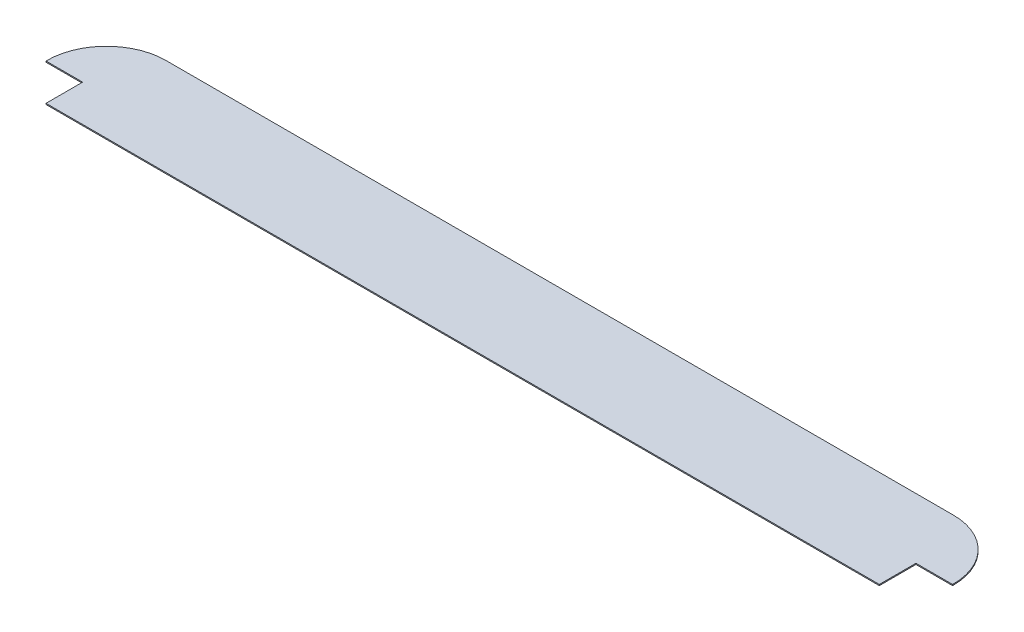
SolidWorks part; units mm, degrees
material "AISI 1020 Steel, Cold Rolled"
ref_plane "Front Plane" through (0, 0, 0) normal (0, 0, 1) x (1, 0, 0)
ref_plane "Top Plane" through (0, 0, 0) normal (0, 1, 0) x (1, 0, 0)
ref_plane "Right Plane" through (0, 0, 0) normal (1, 0, 0) x (0, 0, -1)
sketch "Sketch1" plane through (0, 0, 0) normal (0, 1, 0) x (1, 0, 0)
  line L1 (-455, -53) -> (455, -53)
  line L2 (-495, -13) -> (-495, -12)
  line L3 (-430, 53) -> (430, 53)
  line L4 (495, -13) -> (495, -12)
  line L5 (-455, -48.7172) -> (495, 53) construction
  line L6 (-495, 53) -> (455, -48.7172) construction
  line L9 (-495, -13) -> (-455, -13)
  line L10 (-455, -53) -> (-455, -13)
  line L13 (495, -13) -> (455, -13)
  line L14 (455, -53) -> (455, -13)
  arc A0 (-495, -12) -> (-430, 53) centre (-430, -12) cw
  arc A1 (430, 53) -> (495, -12) centre (430, -12) cw
  point P0 (0, 0)
  dimension "D2" = 65
  dimension "D1" = 990
  dimension "D3" = 40
  dimension "D4" = 40
  dimension "D5" = 40
  dimension "D6" = 40
sheet metal parameters "Sheet-Metal1" thickness 1.2 parameters "D1"=0.7366
base flange "Base-Flange1" sketch "Sketch1" thickness 1.2 reverse thickness direction no parameters "D1"=0.7366
flat pattern "Flat-Pattern1" [suppressed]
sketch "Bend-Lines1" plane through (0, 0, 0) normal (0, 1, 0) x (-1, 0, 0)
